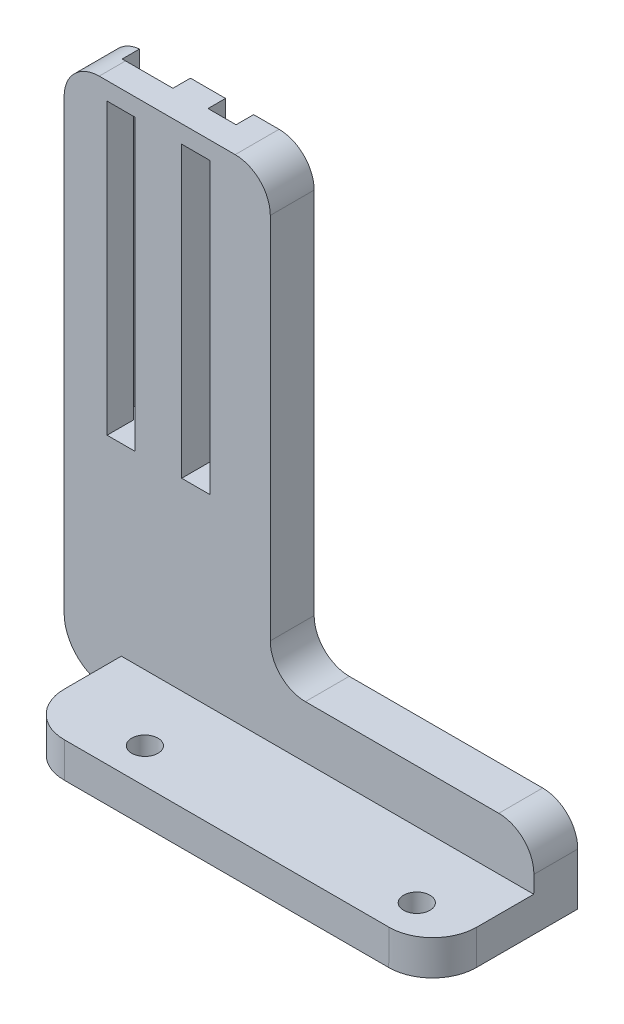
SolidWorks part; units mm, degrees
material "ABS generico"
ref_plane "Front Plane" through (0, 0, 0) normal (0, 0, 1) x (1, 0, 0)
ref_plane "Top Plane" through (0, 0, 0) normal (0, 1, 0) x (1, 0, 0)
ref_plane "Right Plane" through (0, 0, 0) normal (1, 0, 0) x (0, 0, -1)
sketch "Sketch1" plane through (0, 0, 0) normal (0, 0, 1) x (1, 0, 0)
  line L0 (24.5834, -25) -> (24.6606, -15)
  line L1 (24.5834, -25) -> (-28.9167, -25)
  line L2 (-5.4167, 0) -> (-5.4167, 35) construction
  line L3 (-5.4167, 35) -> (-12.3167, 35)
  line L5 (22.0833, -25) -> (-28.9167, 32.7358) construction
  line L6 (24.6606, -15) -> (-5.4167, -15)
  line L7 (-13.9167, 0) -> (-13.9167, 35) construction
  line L8 (-28.9167, -25) -> (-28.9167, 35)
  line L9 (24.5834, -15) -> (-30.9167, -15) construction
  line L10 (-12.3167, 0) -> (-12.3167, 35)
  line L11 (-15.5167, 0) -> (-15.5167, 35)
  line L12 (-5.4167, -15) -> (-5.4167, 35)
  line L13 (-24.0167, 35) -> (-28.9167, 35)
  line L14 (-15.5167, 35) -> (-20.8167, 35)
  line L15 (24.5834, -25) -> (-30.9167, -25) construction
  line L16 (-24.0167, 0) -> (-24.0167, 35)
  line L18 (-18, -10) -> (-18, 25) construction
  line L20 (-20.8167, 0) -> (-20.8167, 35)
  line L22 (-20.8167, 0) -> (-24.0167, 0)
  line L24 (-12.3167, 0) -> (-15.5167, 0)
  line L25 (-15.5167, -15) -> (-15.5167, 35) construction
  line L26 (-13.9167, -15) -> (-13.9167, 35) construction
  line L27 (-12.3167, -15) -> (-12.3167, 35) construction
  point P0 (0, 0)
  point P1 (-30.9167, 35)
  point P3 (26.5, 35)
  point P6 (-18, -25)
  point P10 (-16.4, -25)
  point P12 (-19.6, -25)
  point P18 (22.2762, 0)
  point P19 (-26.5, -10)
  dimension "D3" = 10
  dimension "D7" = 1.6
  dimension "D8" = 1.6
  dimension "D9" = 8.5
extrude "Extrude1" add sketch "Sketch1" along normal blind 5
sketch "Sketch3" plane through (0, 0, 5) normal (0, 0, 1) x (1, 0, 0)
  line L0 (22.0833, -10.5045) -> (22.0833, -32.7354) construction
  line L2 (-15.5167, 0) -> (-15.5167, -46) construction
  line L3 (-15.5167, -23) -> (22.0833, -23) construction
  line L4 (3.2833, -23) -> (3.2833, 0) construction
  line L5 (-15.5167, -25) -> (35.4785, -25) construction
  line L6 (-22.3949, -21) -> (24.6143, -21)
  line L8 (-22.3949, -25) -> (24.5834, -25)
  line L9 (-22.3949, -25) -> (-22.3949, -21)
  line L10 (-15.5167, -21) -> (22.0833, -25) construction
  line L11 (-15.5167, -25) -> (22.0833, -21) construction
  line L12 (24.6143, -21) -> (24.5834, -25)
  line L13 (24.5834, -25) -> (24.6606, -15) construction
  line L14 (-28.9167, -25) -> (24.5834, -25) construction
  dimension "D1" = 2
extrude "Extrude2" add sketch "Sketch3" along normal blind 11.5
sketch "Sketch4" plane through (0, 35, 0) normal (0, 1, 0) x (1, 0, 0)
  line L0 (-20.8167, 0) -> (-24.0167, 0) construction
  line L1 (-25.3167, -2) -> (-19.5167, -2)
  line L2 (-25.3167, -2) -> (-25.3167, 2)
  line L3 (-25.3167, 2) -> (-19.5167, 2)
  line L4 (-19.5167, -2) -> (-19.5167, 2)
  line L5 (-25.3167, -2) -> (-19.5167, 2) construction
  line L6 (-25.3167, 2) -> (-19.5167, -2) construction
  point P0 (-22.4167, 0)
  dimension "D1" = 5.8
  dimension "D2" = 4
sketch "Sketch5" plane through (0, -21, 0) normal (0, 1, 0) x (1, 0, 0)
  line L0 (17.6784, -12.4986) -> (-11.1079, -12.5014) construction
  line L1 (3.2852, -12.5) -> (3.2852, -16.5) construction
  line L2 (-15.5167, -16.5) -> (22.0833, -16.5) construction
  circle A0 centre (-12.2148, -12.5015) radius 1.5
  circle A1 centre (18.7852, -12.5015) radius 1.5
  dimension "D1" = 3
  dimension "D2" = 15.5
  dimension "D3" = 4
extrude "Extrude3" cut sketch "Sketch5" against normal up to surface (4 mm away) up to face at (-9.4529, -25, 8.125)
fillet "Fillet2" radius 5 2 edges at (-22.3949, -23, 16.5) (24.5988, -23, 16.5)
fillet "Fillet3" radius 4 4 edges at (24.6606, -15, 2.5) (-5.4167, -15, 2.5) (-5.4167, 35, 2.5) (-28.9167, 35, 2.5)
fillet "Fillet4" radius 5 1 edges at (-28.9167, -25, 2.5)
extrude "Extrude4" cut sketch "Sketch4" against normal up to surface (35 mm away) up to face at (-22.4167, 0, 2.5)
sketch "Sketch6" plane through (0, 0, 5) normal (0, 0, 1) x (1, 0, 0)
  line L0 (-24.0167, 35) -> (-12.3167, 35)
  line L1 (-12.3167, 35) -> (-12.3167, 32.9851)
  line L2 (-12.3167, 35) -> (-12.3167, 0) construction
  line L3 (-12.3167, 32.9851) -> (-24.0167, 32.9851)
  line L4 (-24.0167, 0) -> (-24.0167, 35) construction
  line L5 (-24.0167, 32.9851) -> (-24.0167, 35)
extrude "Extrude5" add sketch "Sketch6" against normal up to surface (3 mm away) up to face at (-24.7167, 20.997, 2)
